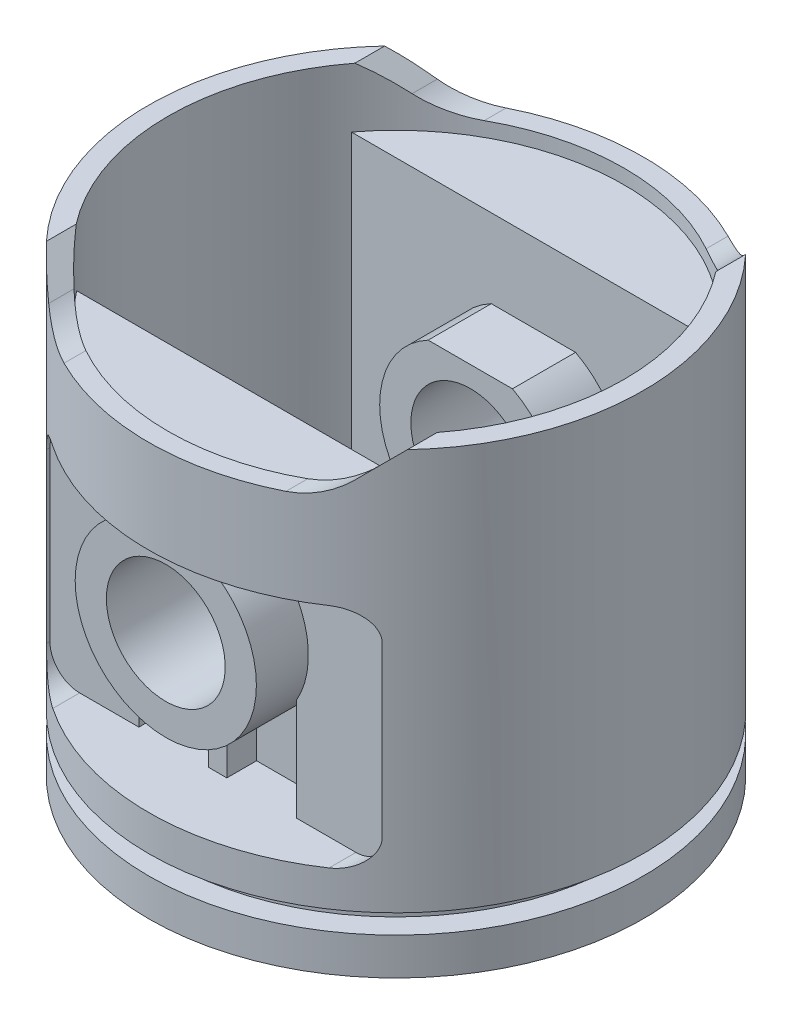
SolidWorks part; units mm, degrees
material "Cast Alloy Steel"
ref_plane "Front Plane" through (0, 0, 0) normal (0, 0, 1) x (1, 0, 0)
ref_plane "Top Plane" through (0, 0, 0) normal (0, 1, 0) x (1, 0, 0)
ref_plane "Right Plane" through (0, 0, 0) normal (1, 0, 0) x (0, 0, -1)
sketch "Sketch1" plane through (0, 0, 0) normal (0, 1, 0) x (1, 0, 0)
  circle A0 centre (0, 0) radius 16.65
  dimension "D1" = 33.3
extrude "Boss-Extrude1" add sketch "Sketch1" along normal blind 2.5
sketch "Sketch2" plane through (0, 2.5, 0) normal (0, 1, 0) x (1, 0, 0)
  circle A0 centre (0, 0) radius 15.15
  circle A1 centre (0, 0) radius 16.65 construction
  dimension "D1" = 1.5
extrude "Boss-Extrude2" add sketch "Sketch2" along normal blind 1.3
sketch "Sketch3" plane through (0, 3.8, 0) normal (0, 1, 0) x (1, 0, 0)
  circle A1 centre (0, 0) radius 16.65
extrude "Boss-Extrude3" add sketch "Sketch3" along normal blind 27
sketch "Sketch4" plane through (0, 0, 0) normal (0, 0, 1) x (1, 0, 0)
  line L0 (-16.65, 30.8) -> (-12.15, 30.8) construction
  line L1 (16.65, 30.8) -> (-16.65, 30.8) construction
  line L2 (0, 0) -> (0, 30.8) construction
  line L3 (-12.15, 30.8) -> (-10.2992, 28.9492)
  line L4 (-7.4708, 27.7776) -> (7.4708, 27.7776)
  line L5 (-12.15, 30.8) -> (12.15, 30.8)
  line L6 (12.15, 30.8) -> (10.2992, 28.9492)
  arc A0 (-10.2992, 28.9492) -> (-7.4708, 27.7776) centre (-7.4708, 31.7776) ccw
  arc A1 (10.2992, 28.9492) -> (7.4708, 27.7776) centre (7.4708, 31.7776) cw
  point P13 (0, 27.7776)
  dimension "D1" = 4
extrude "Cut-Extrude1" cut sketch "Sketch4" against normal blind 27 and the other way blind 27
sketch "Sketch6" plane through (0, 30.8, 0) normal (0, 1, 0) x (1, 0, 0)
  line L0 (0, -9.25) -> (0, 9.25) construction
  line L1 (-12.2499, 9.25) -> (12.2499, 9.25)
  line L2 (-12.2499, -9.25) -> (12.2499, -9.25)
  arc A0 (-12.2499, 9.25) -> (-12.2499, -9.25) centre (0, 0) ccw
  arc A1 (12.15, -11.3842) -> (12.15, 11.3842) centre (0, 0) ccw construction
  arc A2 (12.2499, -9.25) -> (12.2499, 9.25) centre (0, 0) ccw
  point P9 (0, 0)
  point P12 (0, 9.25)
  point P15 (0, -9.25)
  dimension "D1" = 1.3
extrude "Cut-Extrude2" cut sketch "Sketch6" against normal blind 26
ref_plane "Plane1" through (0, 0, 24.5) normal (0, 0, 1) x (1, 0, 0)
sketch "Sketch7" plane through (0, 0, 24.5) normal (0, 0, 1) x (1, 0, 0)
  line L0 (0, 13.85) -> (0, 0) construction
  line L1 (-9.3, 6.2) -> (9.3, 6.2)
  line L2 (-11.3, 8.2) -> (-11.3, 19.5)
  line L3 (-9.3, 21.5) -> (9.3, 21.5)
  line L4 (11.3, 8.2) -> (11.3, 19.5)
  line L5 (-11.3, 6.2) -> (11.3, 21.5) construction
  line L6 (-11.3, 21.5) -> (11.3, 6.2) construction
  line L7 (-16.65, 0) -> (16.65, 0) construction
  arc A0 (9.3, 21.5) -> (11.3, 19.5) centre (9.3, 19.5) cw
  arc A1 (9.3, 6.2) -> (11.3, 8.2) centre (9.3, 8.2) ccw
  arc A2 (-9.3, 6.2) -> (-11.3, 8.2) centre (-9.3, 8.2) cw
  arc A3 (-11.3, 19.5) -> (-9.3, 21.5) centre (-9.3, 19.5) cw
  point P0 (0, 13.85)
  dimension "D4" = 2
  dimension "D1" = 22.6
  dimension "D2" = 15.3
  dimension "D3" = 6.2
extrude "Cut-Extrude3" cut sketch "Sketch7" against normal blind 12.5
mirror "Mirror1" about plane through (0, 0, 0) normal (0, 0, 1) of "Cut-Extrude3"
sketch "Sketch8" plane through (0, 0, -12) normal (0, 0, -1) x (-1, 0, 0)
  line L0 (0, 6.2) -> (0, 10) construction
  line L1 (9.3, 6.2) -> (-9.3, 6.2) construction
  line L2 (-2.8373, 21.5) -> (2.8373, 21.5)
  line L3 (-9.3, 21.5) -> (9.3, 21.5) construction
  circle A0 centre (0, 16.1) radius 4
  arc A1 (-2.8373, 21.5) -> (2.8373, 21.5) centre (0, 16.1) ccw
  dimension "D1" = 3.8
  dimension "D2" = 12.2
  dimension "D3" = 8
extrude "Boss-Extrude4" add sketch "Sketch8" along normal blind 3.5 and the other way blind 7
mirror "Mirror2" about plane through (0, 0, 0) normal (0, 0, 1) of "Boss-Extrude4"
fillet "Fillet1" radius 3 4 edges at (0, 4.8, 9.25) (-15.35, 4.8, 0) (0, 4.8, -9.25) (15.35, 4.8, 0)
sketch "Sketch9" plane through (0, 0, -12) normal (0, 0, -1) x (-1, 0, 0)
  circle A0 centre (0, 16.1) radius 4
extrude "Cut-Extrude4" cut sketch "Sketch9" against normal blind 33.5
sketch "Sketch10" plane through (0, 0, -12) normal (0, 0, -1) x (-1, 0, 0)
  line L0 (0.6118, 6.2) -> (0.6118, 10.0308)
  line L1 (5.3113, 6.2) -> (5.3113, 13.1)
  line L2 (0, 10) -> (0, 6.2) construction
  line L3 (-5.3113, 6.2) -> (-5.3113, 13.1)
  line L4 (-0.6118, 6.2) -> (-0.6118, 10.0308)
  line L5 (9.3, 21.5) -> (2.8373, 21.5)
  line L6 (-2.8373, 21.5) -> (-9.3, 21.5)
  line L7 (-11.3, 19.5) -> (-11.3, 8.2)
  line L8 (-9.3, 6.2) -> (9.3, 6.2)
  line L9 (11.3, 8.2) -> (11.3, 19.5)
  line L13 (-5.3113, 6.2) -> (-0.6118, 6.2)
  line L15 (0.6118, 6.2) -> (5.3113, 6.2)
  arc A1 (0.6118, 10.0308) -> (5.3113, 13.1) centre (0, 16.1) ccw
  arc A5 (-2.8373, 21.5) -> (2.8373, 21.5) centre (0, 16.1) ccw
  arc A6 (-9.3, 21.5) -> (-11.3, 19.5) centre (-9.3, 19.5) ccw
  arc A7 (-11.3, 8.2) -> (-9.3, 6.2) centre (-9.3, 8.2) ccw
  arc A8 (9.3, 6.2) -> (11.3, 8.2) centre (9.3, 8.2) ccw
  arc A9 (11.3, 19.5) -> (9.3, 21.5) centre (9.3, 19.5) ccw
  arc A10 (-5.3113, 13.1) -> (-0.6118, 10.0308) centre (0, 16.1) ccw
  dimension "D1" = 0
extrude "Cut-Extrude5" cut sketch "Sketch10" against normal blind 2
mirror "Mirror3" about plane through (0, 0, 0) normal (0, 0, 1) of "Cut-Extrude5"
sketch "Sketch11" plane through (0, 30.8, 0) normal (0, 1, 0) x (1, 0, 0)
  circle A0 centre (0, 0) radius 15.35
extrude "Cut-Extrude6" cut sketch "Sketch11" against normal blind 4
